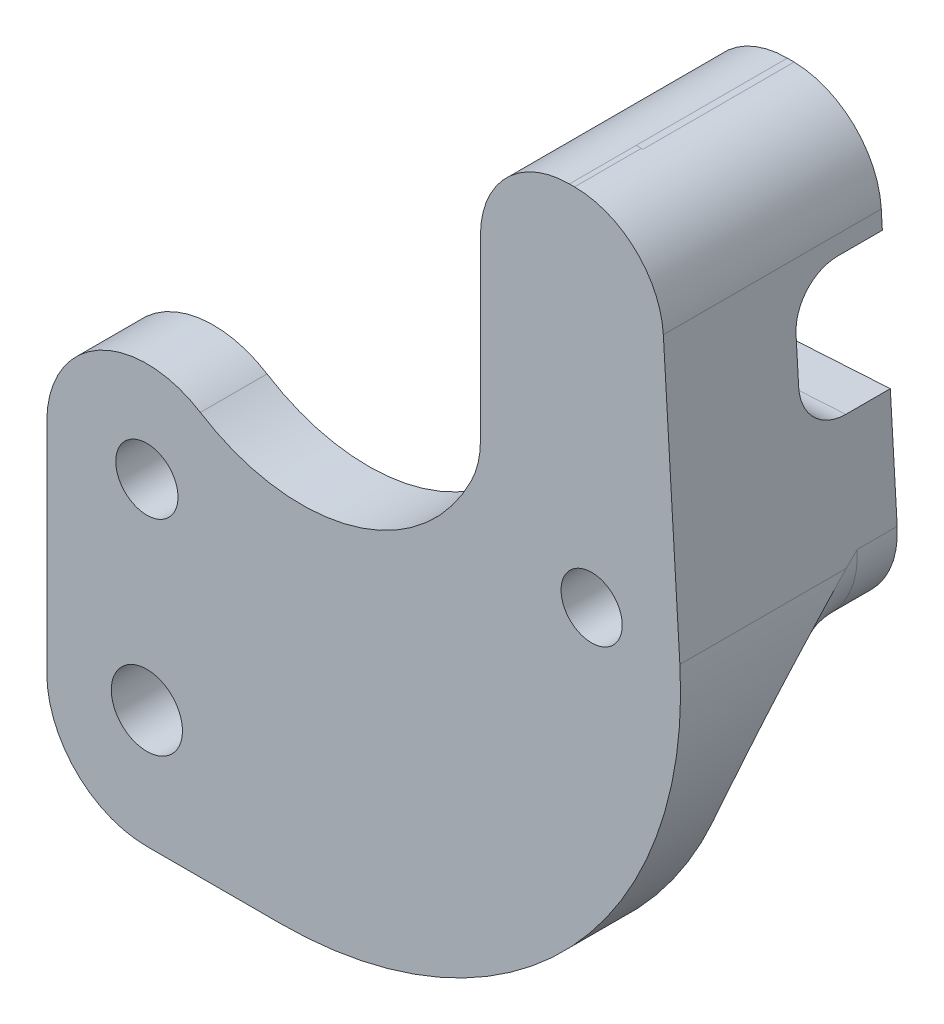
SolidWorks part; units mm, degrees
material "PLA"
ref_plane "Front Plane" through (0, 0, 0) normal (0, 0, 1) x (1, 0, 0)
ref_plane "Top Plane" through (0, 0, 0) normal (0, 1, 0) x (1, 0, 0)
ref_plane "Right Plane" through (0, 0, 0) normal (1, 0, 0) x (0, 0, -1)
sketch "Sketch1" plane through (0, 0, 0) normal (0, 0, 1) x (1, 0, 0)
  line L0 (-4.5, -0.8) -> (-4.5, 9)
  line L1 (20, 14) -> (20, 30) construction
  line L2 (15, 18) -> (15, 30)
  line L3 (15, 30) -> (23, 30)
  line L4 (23.9681, 13.7718) -> (23, 30)
  line L5 (2.7, -1.5588) -> (2.7, 1.5588) construction
  line L6 (0, -5.3) -> (6, -5.3)
  line L7 (2.7, 1.5588) -> (0, 3.1177) construction
  line L8 (0, 3.1177) -> (-2.7, 1.5588) construction
  line L9 (-2.7, 1.5588) -> (-2.7, -1.5588) construction
  line L10 (-2.7, -1.5588) -> (0, -3.1177) construction
  line L11 (0, -3.1177) -> (2.7, -1.5588) construction
  circle A0 centre (0, 0) radius 1.6
  circle A1 centre (0, 9) radius 1.4
  arc A3 (2.4045, 12.8037) -> (-4.5, 9) centre (0, 9) ccw
  arc A4 (15, 18) -> (14.5859, 16.2276) centre (11, 18) cw
  arc A5 (6, -5.3) -> (23.9681, 13.7718) centre (6, 12.7) ccw
  circle A6 centre (0, 0) radius 2.7 construction
  arc A7 (2.4045, 12.8037) -> (14.5859, 16.2276) centre (6.9537, 20) ccw
  circle A8 centre (20, 14) radius 1.375
  circle A9 centre (0, 9) radius 14.3 construction
  arc A10 (-4.5, -0.8) -> (0, -5.3) centre (0, -0.8) ccw
  point P27 (0, -5.3)
  dimension "D2" = 3.2
  dimension "D3" = 2.8
  dimension "D4" = 9
  dimension "D6" = 4
  dimension "D9" = 5.4
  dimension "D14" = 9
  dimension "D15" = 18
  dimension "D16" = 2.75
  dimension "D17" = 28.6
  dimension "D1" = 9
  dimension "D5" = 15
  dimension "D7" = 30
  dimension "D8" = 8
  dimension "D10" = 12
  dimension "D11" = 10
  dimension "D12" = 3
  dimension "D13" = 16
extrude "Boss-Extrude1" add sketch "Sketch1" along normal blind 3
fillet "Fillet1" radius 4 2 edges at (15, 30, 1.5) (23, 30, 1.5)
sketch "Sketch2" plane through (0, 0, 3) normal (0, 0, 1) x (1, 0, 0)
  text T0 "TOP" font "Arial" height 3
extrude "Cut-Extrude1" [suppressed] cut sketch "Sketch2" against normal blind 0.2
sketch "Sketch3" plane through (0, 0, 3) normal (0, 0, 1) x (1, 0, 0)
  line L0 (-2.7, 1.5588) -> (-4.5, 2.5981)
  line L1 (-4.5, 9) -> (-4.5, -0.8) construction
  line L2 (-4.5, 2.5981) -> (-4.5, -6.3792)
  line L3 (0, -3.1177) -> (0, -5.3)
  line L4 (0, -5.3) -> (-4.5, -6.3792)
  line L5 (-2.7, 1.5588) -> (0, 0)
  line L6 (0, 0) -> (0, -3.1177)
extrude "Cut-Extrude2" [suppressed] cut sketch "Sketch3" against normal through all
fillet "Fillet2" [suppressed] radius 1
sketch "Sketch4" plane through (0, 0, 0) normal (0, 0, -1) x (-1, 0, 0)
  line L0 (-23.9404, 14.2351) -> (-23.2244, 26.2382)
  line L1 (-15, 26) -> (-15, 18)
  line L3 (-23.9681, 13.7718) -> (-23.2244, 26.2382) construction
  line L4 (-19.3046, 29.9993) -> (-19, 30)
  circle A0 centre (-20, 14) radius 1.375
  arc A1 (-23.9404, 14.2351) -> (-16.5638, 12.0571) centre (-20, 14) ccw
  circle A2 centre (-20, 14) radius 1.375 construction
  arc A4 (-23.2244, 26.2382) -> (-19.3046, 29.9993) centre (-19.2315, 26) cw
  arc A5 (-15, 18) -> (-14.5859, 16.2276) centre (-11, 18) ccw construction
  arc A7 (-15, 18) -> (-16.5638, 12.0571) centre (-27.0742, 18) cw
  arc A9 (-19.2315, 30) -> (-23.2244, 26.2382) centre (-19.2315, 26) ccw construction
  arc A10 (-19, 30) -> (-15, 26) centre (-19, 26) cw
  arc A11 (-15, 26) -> (-19, 30) centre (-19, 26) ccw construction
extrude "Boss-Extrude2" add sketch "Sketch4" along normal blind 6.8
fillet "Fillet3" radius 5 2 edges at (15.3975, 14.9274, 0)
sketch "Sketch5" plane through (24.7017, 1.4735, 0) normal (0.9982, 0.0595, 0) x (0, 0, -1)
  line L0 (4.8, 22) -> (4.8, 20) construction
  line L1 (-3, 12.3202) -> (4.4794, 12.3202) construction
  line L2 (2.8, 22) -> (2.8, 20)
  line L4 (4.8, 24) -> (6.8, 24)
  line L5 (4.8, 18) -> (6.8, 18)
  line L6 (6.8, 18) -> (6.8, 24)
  arc A0 (4.8, 24) -> (2.8, 22) centre (4.8, 22) ccw
  arc A1 (2.8, 20) -> (4.8, 18) centre (4.8, 20) ccw
  point P2 (4.8, 21)
  dimension "D1" = 2
  dimension "D2" = 2
  dimension "D3" = 2
  dimension "D4" = 21
  dimension "D5" = 5.8
  dimension "D6" = 5.8
  dimension "D7" = 9.8
  dimension "D8" = 5.6798
extrude "Cut-Extrude3" cut sketch "Sketch5" against normal through all
sketch "Sketch6" plane through (0, 0, 0) normal (0, 0, -1) x (-1, 0, 0)
  circle A0 centre (0, 0) radius 1.6
  circle A1 centre (0, 0) radius 3
  dimension "D1" = 3.2
  dimension "D2" = 6
extrude "Boss-Extrude3" add sketch "Sketch6" along normal blind 1.8
fillet "Fillet4" radius 1.8 1 edges at (3, 0, 0)
